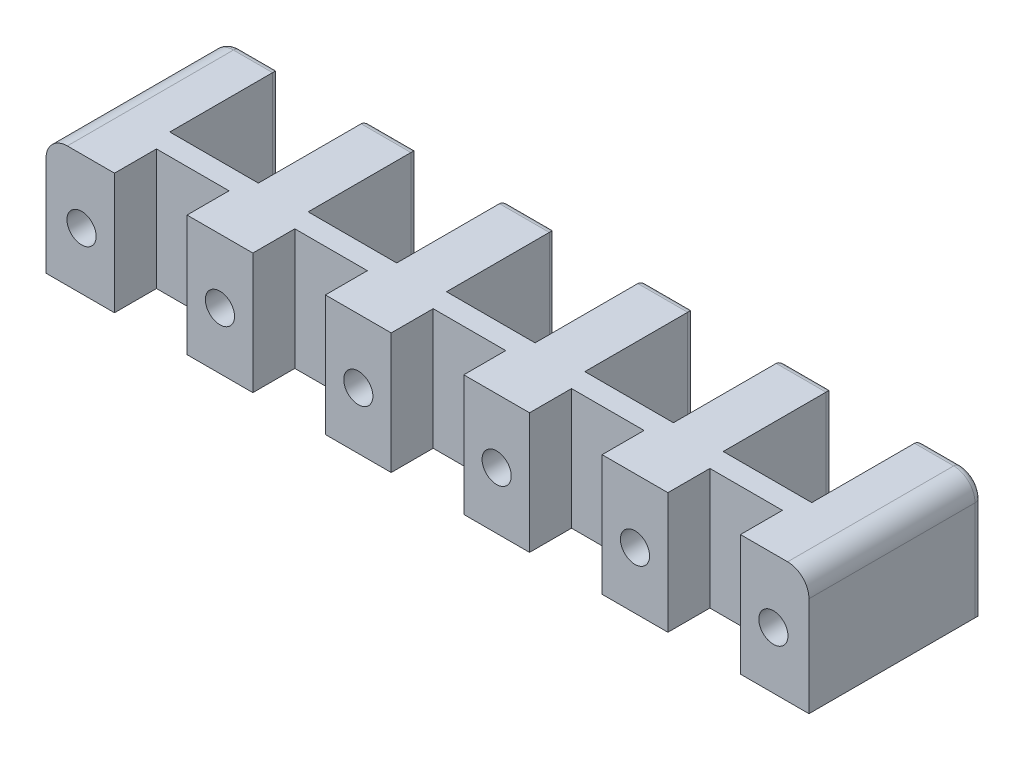
SolidWorks part; units mm, degrees
ref_plane "Front Plane" through (0, 0, 0) normal (0, 0, 1) x (1, 0, 0)
ref_plane "Top Plane" through (0, 0, 0) normal (0, 1, 0) x (1, 0, 0)
ref_plane "Right Plane" through (0, 0, 0) normal (1, 0, 0) x (0, 0, -1)
sketch "Sketch1" plane through (0, 0, 0) normal (0, 1, 0) x (1, 0, 0)
  line L0 (0, 0) -> (-0.0507, 0) construction
  line L1 (19.45, 0) -> (19.3993, 0) construction
  line L2 (-6.225, 10.725) -> (6.225, 10.725)
  line L3 (-6.225, 10.725) -> (-6.225, -10.725)
  line L4 (-6.225, -10.725) -> (6.225, -10.725)
  line L5 (6.225, 10.725) -> (6.225, -10.725)
  line L6 (-6.225, 10.725) -> (6.225, -10.725) construction
  line L7 (-6.225, -10.725) -> (6.225, 10.725) construction
  line L8 (13.225, 10.725) -> (13.225, -10.725)
  line L9 (13.225, 10.725) -> (25.675, 10.725)
  line L10 (25.675, 10.725) -> (25.675, -10.725)
  line L11 (13.225, -10.725) -> (25.675, -10.725)
  line L12 (38.9, 0) -> (38.8493, 0) construction
  line L13 (32.675, 10.725) -> (32.675, -10.725)
  line L14 (32.675, 10.725) -> (45.125, 10.725)
  line L15 (45.125, 10.725) -> (45.125, -10.725)
  line L16 (32.675, -10.725) -> (45.125, -10.725)
  line L17 (58.35, 0) -> (58.2993, 0) construction
  line L18 (52.125, 10.725) -> (52.125, -10.725)
  line L19 (52.125, 10.725) -> (64.575, 10.725)
  line L20 (64.575, 10.725) -> (64.575, -10.725)
  line L21 (52.125, -10.725) -> (64.575, -10.725)
  line L22 (77.8, 0) -> (77.7493, 0) construction
  line L23 (71.575, 10.725) -> (71.575, -10.725)
  line L24 (71.575, 10.725) -> (84.025, 10.725)
  line L25 (84.025, 10.725) -> (84.025, -10.725)
  line L26 (71.575, -10.725) -> (84.025, -10.725)
  line L27 (-19.225, -19.625) -> (-5.1, -19.625)
  line L28 (-9.225, 13.725) -> (87.025, 13.725)
  line L29 (-9.225, 13.725) -> (-9.225, -10.725)
  line L30 (-5.1, -13.725) -> (5.1, -13.725)
  line L31 (87.025, 13.725) -> (87.025, -10.725)
  line L32 (-9.225, 13.725) -> (87.025, -13.725) construction
  line L33 (-9.225, -13.725) -> (87.025, 13.725) construction
  line L34 (-19.225, -19.625) -> (-19.225, -10.725)
  line L35 (-19.225, -10.725) -> (-9.225, -10.725)
  line L36 (87.025, -10.725) -> (97.025, -10.725)
  line L37 (97.025, -10.725) -> (97.025, -19.625)
  line L38 (-5.1, -13.725) -> (-5.1, -19.625)
  line L39 (5.1, -13.725) -> (5.1, -19.625)
  line L40 (5.1, -19.625) -> (14.35, -19.625)
  line L41 (14.35, -19.625) -> (14.35, -13.725)
  line L42 (24.55, -13.725) -> (24.55, -19.625)
  line L43 (24.55, -19.625) -> (33.8, -19.625)
  line L44 (33.8, -19.625) -> (33.8, -13.725)
  line L45 (44, -13.725) -> (44, -19.625)
  line L46 (44, -19.625) -> (53.25, -19.625)
  line L47 (53.25, -19.625) -> (53.25, -13.725)
  line L48 (63.45, -13.725) -> (63.45, -19.625)
  line L49 (63.45, -19.625) -> (72.7, -19.625)
  line L50 (72.7, -19.625) -> (72.7, -13.725)
  line L51 (82.9, -13.725) -> (82.9, -19.625)
  line L52 (5.1, -19.625) -> (14.35, -19.625)
  line L53 (24.55, -19.625) -> (33.8, -19.625)
  line L54 (44, -19.625) -> (53.25, -19.625)
  line L55 (63.45, -19.625) -> (72.7, -19.625)
  line L56 (82.9, -19.625) -> (97.025, -19.625)
  line L57 (14.35, -13.725) -> (24.55, -13.725)
  line L58 (33.8, -13.725) -> (44, -13.725)
  line L59 (53.25, -13.725) -> (63.45, -13.725)
  line L60 (72.7, -13.725) -> (82.9, -13.725)
  line L61 (72.7, -13.725) -> (72.7, -19.625)
  line L62 (63.45, -19.625) -> (63.45, -13.725)
  line L63 (53.25, -13.725) -> (53.25, -19.625)
  line L64 (44, -19.625) -> (44, -13.725)
  line L65 (0, -10.725) -> (0, -17.5719) construction
  line L66 (19.45, -10.725) -> (19.45, -16.6206) construction
  line L67 (38.9, -10.725) -> (38.9, -17.5719) construction
  line L68 (58.35, -10.725) -> (58.35, -17.5719) construction
  line L69 (77.8, -10.725) -> (77.8, -17.5719) construction
  point P71 (0, -13.725)
  point P72 (19.45, -13.725)
  point P73 (38.9, -13.725)
  point P74 (58.35, -13.725)
  point P75 (77.8, -13.725)
  dimension "D1" = 12.45
  dimension "D2" = 21.45
  dimension "D4" = 3
  dimension "D5" = 3
  dimension "D6" = 5.9
  dimension "D7" = 10
  dimension "D8" = 10
  dimension "D9" = 10.2
  dimension "D10" = 10.2
  dimension "D11" = 10.2
  dimension "D12" = 10.2
  dimension "D13" = 10.2
  dimension "D3" = 5
extrude "Boss-Extrude1" add sketch "Sketch1" along normal blind 18 contours L50 L60 L51 L56 L37 L36 L31 L28 L29 L35 L34 L27 L38 L30 L39 L40 L41 L57 L42 L43 L44 L58 L45 L46 L47 L59 L48 L49 L2 L5 L4 L3 L11 L8 L9 L10 L16 L13 L14 L15 L21 L18 L19 L20 L26 L23 region at (-18.0156, 0, 15.175)
sketch "Sketch2" plane through (0, 18, 0) normal (0, 1, 0) x (1, 0, 0)
  line L0 (-9.225, 13.725) -> (-9.225, -10.725) construction
  line L1 (-19.225, -10.725) -> (-9.225, -10.725)
  line L2 (-19.225, -10.725) -> (-19.225, -7.725)
  line L3 (-19.225, -7.725) -> (-9.225, -7.725)
  line L4 (-9.225, -10.725) -> (-9.225, -7.725)
  line L5 (87.025, 13.725) -> (87.025, -10.725) construction
  line L6 (97.025, -10.725) -> (87.025, -10.725)
  line L7 (97.025, -10.725) -> (97.025, -7.725)
  line L8 (97.025, -7.725) -> (87.025, -7.725)
  line L9 (87.025, -10.725) -> (87.025, -7.725)
  dimension "D1" = 3
  dimension "D2" = 3
extrude "Boss-Extrude2" add sketch "Sketch2" against normal up to surface (18 mm away) up to face at (0, 0, 0)
sketch "Sketch4" plane through (0, 18, 0) normal (0, 1, 0) x (1, 0, 0)
  line L0 (-6.225, 10.725) -> (6.225, 10.725) construction
  line L1 (-3.5, 14.8177) -> (3.5, 14.8177)
  line L2 (-3.5, 14.8177) -> (-3.5, 6.6323)
  line L3 (-3.5, 6.6323) -> (3.5, 6.6323)
  line L4 (3.5, 14.8177) -> (3.5, 6.6323)
  line L5 (-3.5, 14.8177) -> (3.5, 6.6323) construction
  line L6 (-3.5, 6.6323) -> (3.5, 14.8177) construction
  line L7 (13.225, 10.725) -> (25.675, 10.725) construction
  line L8 (15.95, 15.2856) -> (22.95, 15.2856)
  line L9 (15.95, 15.2856) -> (15.95, 6.1644)
  line L10 (15.95, 6.1644) -> (22.95, 6.1644)
  line L11 (22.95, 15.2856) -> (22.95, 6.1644)
  line L12 (15.95, 15.2856) -> (22.95, 6.1644) construction
  line L13 (15.95, 6.1644) -> (22.95, 15.2856) construction
  line L14 (32.675, 10.725) -> (45.125, 10.725) construction
  line L15 (35.4, 17.4328) -> (42.4, 17.4328)
  line L16 (35.4, 17.4328) -> (35.4, 4.0172)
  line L17 (35.4, 4.0172) -> (42.4, 4.0172)
  line L18 (42.4, 17.4328) -> (42.4, 4.0172)
  line L19 (35.4, 17.4328) -> (42.4, 4.0172) construction
  line L20 (35.4, 4.0172) -> (42.4, 17.4328) construction
  line L21 (52.125, 10.725) -> (64.575, 10.725) construction
  line L22 (54.85, 15.7825) -> (61.85, 15.7825)
  line L23 (54.85, 15.7825) -> (54.85, 5.6675)
  line L24 (54.85, 5.6675) -> (61.85, 5.6675)
  line L25 (61.85, 15.7825) -> (61.85, 5.6675)
  line L26 (54.85, 15.7825) -> (61.85, 5.6675) construction
  line L27 (54.85, 5.6675) -> (61.85, 15.7825) construction
  line L28 (71.575, 10.725) -> (84.025, 10.725) construction
  line L29 (74.3, 15.0129) -> (81.3, 15.0129)
  line L30 (74.3, 15.0129) -> (74.3, 6.4371)
  line L31 (74.3, 6.4371) -> (81.3, 6.4371)
  line L32 (81.3, 15.0129) -> (81.3, 6.4371)
  line L33 (74.3, 15.0129) -> (81.3, 6.4371) construction
  line L34 (74.3, 6.4371) -> (81.3, 15.0129) construction
  point P0 (0, 10.725)
  point P7 (19.45, 10.725)
  point P14 (38.9, 10.725)
  point P21 (58.35, 10.725)
  point P28 (77.8, 10.725)
  dimension "D1" = 7
  dimension "D2" = 7
  dimension "D3" = 7
  dimension "D4" = 7
  dimension "D5" = 7
extrude "Cut-Extrude2" cut sketch "Sketch4" against normal blind 6
fillet "Fillet3" radius 3.5 10 edges at (81.3, 12, -12.225) (74.3, 12, -12.225) (54.85, 12, -12.225) (61.85, 12, -12.225) (42.4, 12, -12.225) (35.4, 12, -12.225) (15.95, 12, -12.225) (22.95, 12, -12.225) (3.5, 12, -12.225) (-3.5, 12, -12.225)
fillet "Fillet4" radius 2 10 edges at (35.4, 18, -12.225) (54.85, 18, -12.225) (74.3, 18, -12.225) (81.3, 18, -12.225) (61.85, 18, -12.225) (42.4, 18, -12.225) (22.95, 18, -12.225) (15.95, 18, -12.225) (3.5, 18, -12.225) (-3.5, 18, -12.225)
sketch "Sketch5" plane through (0, 0, 19.625) normal (0, 0, 1) x (1, 0, 0)
  line L0 (-19.225, 9) -> (97.025, 9) construction
  line L1 (-19.225, 18) -> (-19.225, 0) construction
  line L2 (97.025, 18) -> (97.025, 0) construction
  line L3 (5.1, 9) -> (14.35, 9) construction
  line L4 (5.1, 18) -> (5.1, 0) construction
  line L5 (14.35, 18) -> (14.35, 0) construction
  line L6 (24.55, 9) -> (33.8, 9) construction
  line L7 (24.55, 18) -> (24.55, 0) construction
  line L8 (33.8, 18) -> (33.8, 0) construction
  line L9 (44, 9) -> (53.25, 9) construction
  line L10 (44, 18) -> (44, 0) construction
  line L11 (53.25, 18) -> (53.25, 0) construction
  line L12 (63.45, 9) -> (72.7, 9) construction
  line L13 (63.45, 18) -> (63.45, 0) construction
  line L14 (72.7, 18) -> (72.7, 0) construction
  line L15 (-5.1, 18) -> (-5.1, 0) construction
  line L16 (82.9, 18) -> (82.9, 0) construction
  circle A0 centre (9.725, 9) radius 1.6
  circle A1 centre (29.175, 9) radius 1.6
  circle A2 centre (48.625, 9) radius 1.6
  circle A3 centre (68.075, 9) radius 1.6
  circle A4 centre (87.53, 9) radius 1.6
  circle A5 centre (-9.73, 9) radius 1.6
  dimension "D1" = 3.2
  dimension "D2" = 3.2
  dimension "D3" = 3.2
  dimension "D4" = 3.2
  dimension "D5" = 3.2
  dimension "D6" = 3.2
  dimension "D7" = 4.63
  dimension "D8" = 4.63
extrude "Cut-Extrude3" cut sketch "Sketch5" against normal through all
sketch "Sketch7" plane through (0, 0, -13.725) normal (0, 0, -1) x (-1, 0, 0)
  line L0 (-87.53, 9) -> (-92.53, 9) construction
  line L1 (9.73, 9) -> (14.73, 9) construction
  line L2 (-92.53, 9) -> (-92.53, -2.9346)
  line L3 (-92.53, -2.9346) -> (-102.871, -2.9346)
  line L4 (-102.871, -2.9346) -> (-102.871, 21.3195)
  line L5 (-102.871, 21.3195) -> (-92.53, 21.3195)
  line L6 (-92.53, 21.3195) -> (-92.53, 9)
  line L7 (14.73, 9) -> (14.73, -3.3373)
  line L8 (14.73, -3.3373) -> (26.9404, -3.3373)
  line L9 (26.9404, -3.3373) -> (26.9404, 20.1807)
  line L10 (26.9404, 20.1807) -> (14.73, 20.1807)
  line L11 (14.73, 20.1807) -> (14.73, 9)
  dimension "D1" = 5
  dimension "D2" = 5
extrude "Cut-Extrude4" cut sketch "Sketch7" against normal through all
sketch "Sketch10" plane through (0, 0, 7.725) normal (0, 0, -1) x (-1, 0, 0)
  line L0 (-83.3, 18) -> (-87.025, 18) construction
  line L1 (-85.1625, 18) -> (-92.53, 18)
  line L2 (-85.1625, 18) -> (-85.1625, 0)
  line L3 (-85.1625, 0) -> (-92.53, 0)
  line L4 (-92.53, 18) -> (-92.53, 0)
  line L5 (9.225, 18) -> (5.5, 18) construction
  line L6 (14.73, 0) -> (7.3625, 0)
  line L7 (14.73, 0) -> (14.73, 18)
  line L8 (14.73, 18) -> (7.3625, 18)
  line L9 (7.3625, 0) -> (7.3625, 18)
  circle A0 centre (-87.53, 9) radius 1.6
  circle A1 centre (9.73, 9) radius 1.6
extrude "Boss-Extrude4" add sketch "Sketch10" along normal up to surface (21.45 mm away) up to face at (38.9, 14.5091, -13.725)
fillet "Fillet6" radius 3 2 edges at (-14.73, 18, 2.95) (92.53, 18, 2.95)
sketch "Sketch11" plane through (0, 18, 0) normal (0, 1, 0) x (1, 0, 0)
  line L1 (-18.1321, 4.725) -> (96.0074, 4.725)
  line L2 (-18.1321, 4.725) -> (-18.1321, 5.725)
  line L3 (-18.1321, 5.725) -> (96.0074, 5.725)
  line L4 (96.0074, 4.725) -> (96.0074, 5.725)
  line L5 (-11.73, 13.725) -> (-5.5, 13.725) construction
  dimension "D1" = 8
  dimension "D2" = 1
extrude "Cut-Extrude5" cut sketch "Sketch11" against normal through all
chamfer "Chamfer1" distance 1 angle 45 24 edges at (38.9, 0, -13.725) (-14.73, 0, -9.725) (-10.4775, 0, -5.725) (-6.225, 0, -8.225) (0, 0, -10.725) (6.225, 0, -8.225) (9.725, 0, -5.725) (13.225, 0, -8.225) (19.45, 0, -10.725) (25.675, 0, -8.225) (29.175, 0, -5.725) (32.675, 0, -8.225) (38.9, 0, -10.725) (45.125, 0, -8.225) (48.625, 0, -5.725) (52.125, 0, -8.225) (58.35, 0, -10.725) (64.575, 0, -8.225) (68.075, 0, -5.725) (71.575, 0, -8.225) (77.8, 0, -10.725) (84.025, 0, -8.225) (88.2775, 0, -5.725) (92.53, 0, -9.725)
chamfer "Chamfer2" distance 1 angle 45 44 edges at (-9.915, 0, 19.625) (-5.1, 0, 16.675) (0, 0, 13.725) (5.1, 0, 16.675) (9.725, 0, 19.625) (14.35, 0, 16.675) (19.45, 0, 13.725) (24.55, 0, 16.675) (29.175, 0, 19.625) (33.8, 0, 16.675) (38.9, 0, 13.725) (44, 0, 16.675) (48.625, 0, 19.625) (53.25, 0, 16.675) (58.35, 0, 13.725) (63.45, 0, 16.675) (68.075, 0, 19.625) (72.7, 0, 16.675) (77.8, 0, 13.725) (82.9, 0, 16.675) (87.715, 0, 19.625) (92.53, 0, 7.45) (88.2775, 0, -4.725) (84.025, 0, 3) (77.8, 0, 10.725) (71.575, 0, 3) (68.075, 0, -4.725) (64.575, 0, 3) (58.35, 0, 10.725) (52.125, 0, 3) (48.625, 0, -4.725) (45.125, 0, 3) (38.9, 0, 10.725) (32.675, 0, 3) (29.175, 0, -4.725) (25.675, 0, 3) (19.45, 0, 10.725) (13.225, 0, 3) (9.725, 0, -4.725) (6.225, 0, 3) (0, 0, 10.725) (-6.225, 0, 3) (-10.4775, 0, -4.725) (-14.73, 0, 7.45)
fillet "Fillet7" radius 1 20 edges at (92.53, 8, -4.725) (91.6513, 17.1213, -4.725) (-8.9775, 18, -4.725) (-13.8513, 17.1213, -4.725) (86.7775, 18, -4.725) (68.075, 18, -4.725) (48.625, 18, -4.725) (29.175, 18, -4.725) (9.725, 18, -4.725) (-14.73, 8, -4.725) (-6.225, 9.5, -4.725) (6.225, 9.5, -4.725) (13.225, 9.5, -4.725) (32.675, 9.5, -4.725) (52.125, 9.5, -4.725) (25.675, 9.5, -4.725) (45.125, 9.5, -4.725) (64.575, 9.5, -4.725) (71.575, 9.5, -4.725) (84.025, 9.5, -4.725)
fillet "Fillet8" radius 1 20 edges at (92.53, 8, -5.725) (91.6513, 17.1213, -5.725) (-14.73, 8, -5.725) (-13.8513, 17.1213, -5.725) (86.7775, 18, -5.725) (84.025, 9.5, -5.725) (64.575, 9.5, -5.725) (68.075, 18, -5.725) (71.575, 9.5, -5.725) (52.125, 9.5, -5.725) (48.625, 18, -5.725) (45.125, 9.5, -5.725) (25.675, 9.5, -5.725) (29.175, 18, -5.725) (32.675, 9.5, -5.725) (13.225, 9.5, -5.725) (9.725, 18, -5.725) (6.225, 9.5, -5.725) (-8.9775, 18, -5.725) (-6.225, 9.5, -5.725)
fillet "Fillet9" radius 1 40 edges at (-14.73, 8, -13.725) (-13.8513, 17.1213, -13.725) (-8.615, 18, -13.725) (-4.0858, 17.4142, -13.725) (-3.5, 15.75, -13.725) (-2.4749, 13.0251, -13.725) (2.4749, 13.0251, -13.725) (3.5, 15.75, -13.725) (4.0858, 17.4142, -13.725) (9.725, 18, -13.725) (15.3642, 17.4142, -13.725) (15.95, 15.75, -13.725) (16.9751, 13.0251, -13.725) (21.9249, 13.0251, -13.725) (22.95, 15.75, -13.725) (23.5358, 17.4142, -13.725) (29.175, 18, -13.725) (34.8142, 17.4142, -13.725) (35.4, 15.75, -13.725) (36.4251, 13.0251, -13.725) (41.3749, 13.0251, -13.725) (42.4, 15.75, -13.725) (42.9858, 17.4142, -13.725) (48.625, 18, -13.725) (54.2642, 17.4142, -13.725) (54.85, 15.75, -13.725) (55.8751, 13.0251, -13.725) (60.8249, 13.0251, -13.725) (61.85, 15.75, -13.725) (62.4358, 17.4142, -13.725) (68.075, 18, -13.725) (73.7142, 17.4142, -13.725) (74.3, 15.75, -13.725) (75.3251, 13.0251, -13.725) (80.2749, 13.0251, -13.725) (81.3, 15.75, -13.725) (81.8858, 17.4142, -13.725) (86.415, 18, -13.725) (91.6513, 17.1213, -13.725) (92.53, 8, -13.725)
sketch "Sketch13" plane through (0, 0, 19.625) normal (0, 0, 1) x (1, 0, 0)
  circle A0 centre (-9.73, 9) radius 2.05
  circle A1 centre (9.725, 9) radius 2.05
  circle A2 centre (29.175, 9) radius 2.05
  circle A3 centre (48.625, 9) radius 2.05
  circle A4 centre (68.075, 9) radius 2.05
  circle A5 centre (87.53, 9) radius 2.05
  dimension "D1" = 4.1
  dimension "D2" = 4.1
  dimension "D3" = 4.1
  dimension "D4" = 4.1
  dimension "D5" = 4.1
  dimension "D6" = 4.1
extrude "Cut-Extrude6" cut sketch "Sketch13" against normal blind 8
sketch "Sketch14" plane through (0, 0, -4.725) normal (0, 0, -1) x (-1, 0, 0)
  circle A0 centre (-87.53, 9) radius 2.05
  circle A1 centre (-68.075, 9) radius 2.05
  circle A2 centre (-48.625, 9) radius 2.05
  circle A3 centre (-29.175, 9) radius 2.05
  circle A4 centre (-9.725, 9) radius 2.05
  circle A5 centre (9.73, 9) radius 2.05
  dimension "D1" = 4.1
  dimension "D2" = 4.1
  dimension "D3" = 4.1
  dimension "D4" = 4.1
  dimension "D5" = 4.1
  dimension "D6" = 4.1
extrude "Cut-Extrude7" cut sketch "Sketch14" against normal blind 10
sketch "Sketch15" plane through (0, 0, 0) normal (0, -1, 0) x (1, 0, 0)
  line L1 (-20.277, -5.2294) -> (93.7234, -5.2294)
  line L2 (-20.277, -5.2294) -> (-20.277, -38.373)
  line L3 (-20.277, -38.373) -> (93.7234, -38.373)
  line L4 (93.7234, -5.2294) -> (93.7234, -38.373)
extrude "Cut-Extrude9" cut sketch "Sketch15" against normal through all
